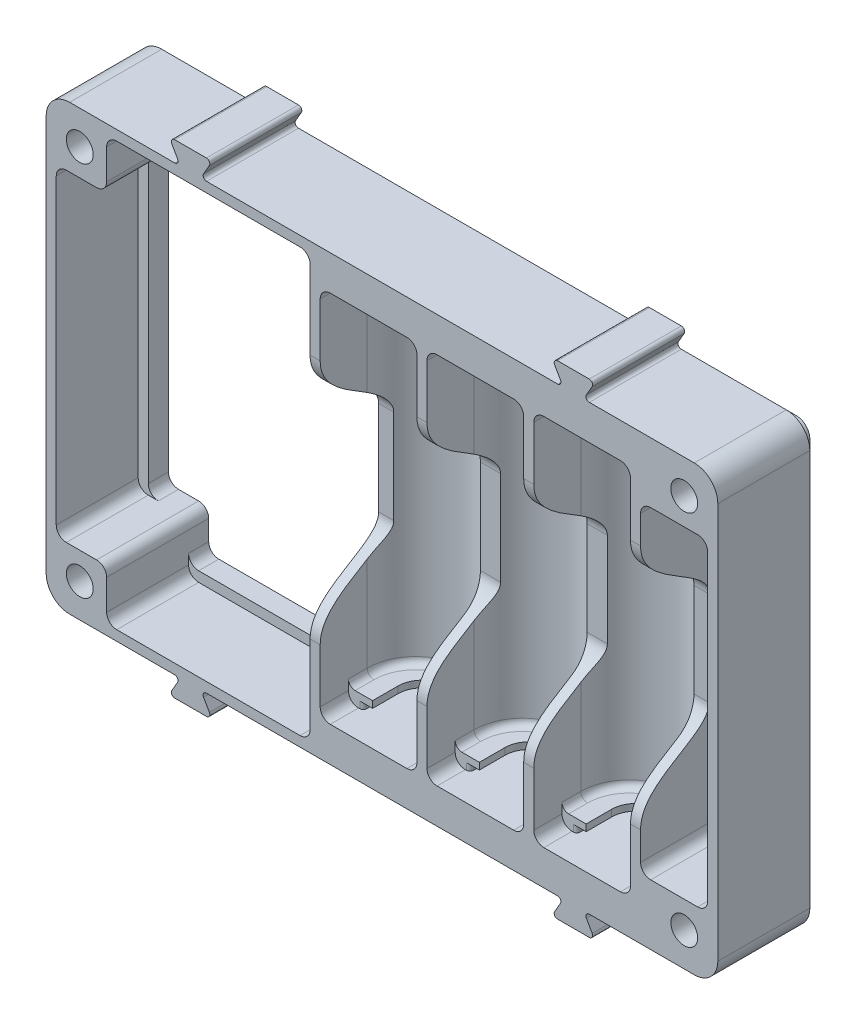
SolidWorks part; units mm, degrees
material "ABS"
ref_plane "Front Plane" through (0, 0, 0) normal (0, 0, 1) x (1, 0, 0)
ref_plane "Top Plane" through (0, 0, 0) normal (0, 1, 0) x (1, 0, 0)
ref_plane "Right Plane" through (0, 0, 0) normal (1, 0, 0) x (0, 0, -1)
sketch "Sketch1" plane through (0, 0, 0) normal (0, 1, 0) x (1, 0, 0)
  line L0 (-24.6, 0) -> (24.6, 0)
  line L1 (0, 0) -> (0, -8.2) construction
  line L2 (-5.4908, -1) -> (5.6475, -1) construction
  line L3 (7, -12.213) -> (7, -2.6204) construction
  line L4 (8.9, -12.0066) -> (8.9, -2.0587) construction
  line L5 (0, -8.2) -> (15.9, -8.2) construction
  line L6 (7.2, -8.2) -> (7.2, -15.2)
  line L7 (8.7, -8.2) -> (8.7, -15.2)
  line L8 (8.7, -15.2) -> (23.1, -15.2) construction
  line L9 (8.7, -15.2) -> (7.2, -15.2)
  line L10 (-1.7094, -15.2) -> (7.2, -15.2) construction
  line L11 (15.9, -8.2) -> (23.1, -8.2) construction
  line L12 (23.1, -15.2) -> (23.1, -8.2)
  line L13 (23.1, -15.2) -> (24.6, -15.2)
  line L14 (24.6, -15.2) -> (24.6, 0)
  line L15 (-24.6, -15.2) -> (-24.6, 0)
  line L16 (-23.1, -15.2) -> (-24.6, -15.2)
  line L17 (-23.1, -15.2) -> (-23.1, -8.2)
  line L18 (-8.7, -8.2) -> (-8.7, -15.2)
  line L19 (-8.7, -15.2) -> (-7.2, -15.2)
  line L20 (-7.2, -8.2) -> (-7.2, -15.2)
  circle A0 centre (0, -8.2) radius 7 construction
  arc A1 (-7.2, -8.2) -> (7.2, -8.2) centre (0, -8.2) cw
  circle A2 centre (15.9, -8.2) radius 7 construction
  arc A3 (8.7, -8.2) -> (23.1, -8.2) centre (15.9, -8.2) cw
  arc A4 (-8.7, -8.2) -> (-23.1, -8.2) centre (-15.9, -8.2) ccw
  dimension "D1" = 14
  dimension "D2" = 0.2
  dimension "D3" = 1
  dimension "D4" = 1.5
  dimension "D5" = 15.2
  dimension "D6" = 15.9
extrude "Boss-Extrude1" add sketch "Sketch1" along normal blind 27.8
sketch "Sketch2" plane through (0, 27.8, 0) normal (0, -1, 0) x (1, 0, 0)
  line L1 (-24.6, 15.2) -> (24.6, 15.2)
  line L2 (-24.6, 15.2) -> (-24.6, 0)
  line L3 (-24.6, 0) -> (24.6, 0)
  line L4 (24.6, 15.2) -> (24.6, 0)
extrude "Boss-Extrude2" add sketch "Sketch2" against normal blind 1.5
ref_plane "Plane1" through (-15.9, 0, 0) normal (1, 0, 0) x (0, 0, -1)
ref_plane "Plane3" through (15.9, 0, 0) normal (1, 0, 0) x (0, 0, -1)
sketch "Sketch6" plane through (0, 0, 0) normal (1, 0, 0) x (0, 0, -1)
  line L0 (-5, 0) -> (-15.2, 0)
  line L1 (-15.2, 0) -> (0, 0) construction
  line L2 (-15.2, 0) -> (-15.2, 18.3)
  line L3 (-15.2, 29.3) -> (-15.2, 0) construction
  line L4 (-5, 0) -> (-5, 7)
  line L5 (0, 29.3) -> (0, 0) construction
  line L6 (0, 29.3) -> (-15.2, 29.3) construction
  spline S0 degree 3 poles (-15.2, 18.3) (-15.2, 12.3) (-5, 11) (-5, 7) knots 0 0 0 0 1 1 1 1
  dimension "D4" = 12
  dimension "D5" = 18
  dimension "D1" = 7
  dimension "D2" = 5
  dimension "D3" = 11
extrude "Cut-Extrude2" cut sketch "Sketch6" against normal through all both and the other way through all
sketch "Sketch3" plane through (0, 27.8, 0) normal (0, -1, 0) x (1, 0, 0)
  line L0 (-10.4, 11) -> (-8.7, 11)
  line L1 (-8.7, 8.2) -> (-8.7, 15.2) construction
  line L2 (-8.7, 11) -> (-8.7, 0)
  line L3 (24.6, 0) -> (-24.6, 0) construction
  line L4 (-8.7, 0) -> (-23.1, 0)
  line L6 (-20.4, 2.9) -> (-11.4, 2.9)
  line L7 (-10.9, 3.4) -> (-10.9, 10.5)
  line L8 (-15.9, 15.2) -> (-15.9, 0) construction
  line L9 (-8.7, 15.2) -> (-23.1, 15.2) construction
  line L19 (-23.1, 11) -> (-23.1, 0)
  line L20 (-21.4, 11) -> (-23.1, 11)
  line L21 (-20.9, 3.4) -> (-20.9, 10.5)
  arc A1 (-11.4, 2.9) -> (-10.9, 3.4) centre (-11.4, 3.4) ccw
  arc A4 (-10.4, 11) -> (-10.9, 10.5) centre (-10.4, 10.5) ccw
  arc A6 (-20.4, 2.9) -> (-20.9, 3.4) centre (-20.4, 3.4) cw
  arc A7 (-21.4, 11) -> (-20.9, 10.5) centre (-21.4, 10.5) cw
  dimension "D6" = 0.5
  dimension "D7" = 0.5
  dimension "D1" = 5
  dimension "D2" = 11
  dimension "D3" = 2.9
extrude "Inner" add sketch "Sketch3" along normal blind 1
sketch "Sketch4" plane through (0, 26.8, 0) normal (0, -1, 0) x (1, 0, 0)
  line L1 (-8.7, 8.2) -> (-8.7, 15.2) construction
  line L2 (-8.7, 11) -> (-8.7, 0)
  line L3 (24.6, 0) -> (-24.6, 0) construction
  line L4 (-8.7, 0) -> (-23.1, 0)
  line L5 (-23.1, 0) -> (-23.1, 11)
  line L6 (-8.7, 11) -> (-10.4, 11) construction
  line L7 (-23.1, 11) -> (-19.5, 11)
  line L8 (-19.5, 11) -> (-19.5, 7.2)
  line L10 (-12.3, 7.2) -> (-12.3, 11)
  line L11 (-12.3, 11) -> (-8.7, 11)
  arc A0 (-19.5, 7.2) -> (-12.3, 7.2) centre (-15.9, 7.2) ccw
  dimension "D1" = 3.6
  dimension "D2" = 3.8
extrude "Boss-Extrude4" add sketch "Sketch4" along normal blind 1
sketch "Sketch5" plane through (0, 0, 15.2) normal (0, 0, 1) x (1, 0, 0)
  line L0 (-8.7, 27.8) -> (-23.1, 27.8) construction
  line L1 (-17.6, 27.8) -> (-14.2, 27.8)
  line L2 (-17.6, 27.8) -> (-17.6, 27.3)
  line L3 (-17.6, 27.3) -> (-14.2, 27.3)
  line L4 (-14.2, 27.8) -> (-14.2, 27.3)
  point P10 (-15.9, 27.8)
  dimension "D1" = 0.5
  dimension "D2" = 3.4
extrude "Cut-Extrude1" cut sketch "Sketch5" against normal through all
sketch "Sketch10" plane through (0, 0, 0) normal (0, 0, 1) x (1, 0, 0)
  line L0 (-24.6, 29.3) -> (24.6, 29.3) construction
  line L1 (-14.2, 27.3) -> (-17.6, 27.3)
  line L2 (-14.2, 27.3) -> (-14.2, 29.3)
  line L3 (-14.2, 29.3) -> (-17.6, 29.3)
  line L4 (-17.6, 27.3) -> (-17.6, 29.3)
extrude "Cut-Extrude6" cut sketch "Sketch10" along normal blind 0.6
mirror "Mirror1" about plane through (0, 0, 0) normal (1, 0, 0) of "Cut-Extrude6", "Inner", "Boss-Extrude4", "Cut-Extrude1"
ref_plane "Plane2" through (-7.95, 0, 0) normal (1, 0, 0) x (0, 0, -1)
mirror "Mirror2" about plane through (-7.95, 0, 0) normal (1, 0, 0) of "Cut-Extrude6", "Inner", "Boss-Extrude4", "Cut-Extrude1"
fillet "Fillet2" radius 1.5 6 edges at (-8.7, 27.8, 13.1) (-23.1, 27.8, 13.1) (8.7, 27.8, 13.1) (23.1, 27.8, 13.1) (7.2, 27.8, 13.1) (-7.2, 27.8, 13.1)
fillet "Fillet3" radius 1 9 edges at (-8.7, 25.8, 9.6) (-15.9, 25.8, 1) (-23.1, 25.8, 9.6) (23.1, 25.8, 9.6) (8.7, 25.8, 9.6) (7.2, 25.8, 9.6) (-7.2, 25.8, 9.6) (15.9, 25.8, 1) (0, 25.8, 1)
mirror "Mirror4" about plane through (0, 0, 0) normal (0, 1, 0) of bodies 108 110
sketch "Эскиз1" plane through (0, 0, 0) normal (0, 0, -1) x (-1, 0, 0)
  line L0 (-24.6, 29.3) -> (-24.6, -29.3) construction
  line L5 (-36.1, 33) -> (63.9, 33)
  line L6 (-36.1, 33) -> (-36.1, -33)
  line L7 (-36.1, -33) -> (63.9, -33)
  line L8 (63.9, 33) -> (63.9, -33)
  line L9 (-36.1, 33) -> (63.9, -33) construction
  line L10 (-36.1, -33) -> (63.9, 33) construction
  line L11 (-34.6, -31.5) -> (62.4, -31.5)
  line L12 (-34.6, -31.5) -> (-34.6, 31.5)
  line L13 (-34.6, 31.5) -> (62.4, 31.5)
  line L14 (62.4, -31.5) -> (62.4, 31.5)
  line L15 (-34.6, -31.5) -> (62.4, 31.5) construction
  line L16 (-34.6, 31.5) -> (62.4, -31.5) construction
  line L17 (24.6, 29.3) -> (24.6, -29.3) construction
  line L18 (-24.6, 29.3) -> (24.6, 29.3)
  line L19 (-24.6, 29.3) -> (-24.6, 31.5)
  line L20 (-24.6, 31.5) -> (24.6, 31.5)
  line L21 (24.6, 29.3) -> (24.6, 31.5)
  line L22 (-24.6, -29.3) -> (24.6, -29.3)
  line L23 (-24.6, -29.3) -> (-24.6, -31.5)
  line L24 (-24.6, -31.5) -> (24.6, -31.5)
  line L25 (24.6, -29.3) -> (24.6, -31.5)
  line L27 (-24.6, 29.3) -> (-24.6, -29.3) construction
  line L28 (62.4, 31.5) -> (54.9, 31.5)
  line L29 (62.4, 31.5) -> (62.4, 24)
  line L30 (62.4, 24) -> (54.9, 24)
  line L31 (54.9, 31.5) -> (54.9, 24)
  line L32 (62.4, -31.5) -> (54.9, -31.5)
  line L33 (62.4, -31.5) -> (62.4, -24)
  line L34 (62.4, -24) -> (54.9, -24)
  line L35 (54.9, -31.5) -> (54.9, -24)
  line L36 (-34.6, 31.5) -> (-24.6, 31.5)
  line L37 (-34.6, 31.5) -> (-34.6, 24)
  line L38 (-34.6, 24) -> (-24.6, 24)
  line L39 (-24.6, 31.5) -> (-24.6, 24)
  line L41 (-34.6, -31.5) -> (-24.6, -31.5)
  line L42 (-34.6, -31.5) -> (-34.6, -24)
  line L43 (-34.6, -24) -> (-24.6, -24)
  line L44 (-24.6, -31.5) -> (-24.6, -24)
  point P0 (13.9, 0)
  point P5 (13.9, 0)
  point P13 (0, 0)
  line M16 (24.6, 29.3) -> (17.6, 29.3)
  line M20 (14.2, 29.3) -> (1.7, 29.3)
  line M24 (-1.7, 29.3) -> (-14.2, 29.3)
  line M28 (-17.6, 29.3) -> (-24.6, 29.3)
  line M30 (-24.6, 29.3) -> (-24.6, -29.3)
  dimension "D1" = 100
  dimension "D2" = 66
  dimension "D3" = 1.5
  dimension "D4" = 1.5
  dimension "D5" = 10
  dimension "D6" = 7.5
extrude "Бобышка-Вытянуть1" add sketch "Эскиз1" against normal up to surface (15.2 mm away) contours L13 L31 L30 L14 | L35 L11 L14 L34 | L43 L12 L11 L23 M30 | L12 L38 L19 L13 M30 | L8 L5 L6 L7 L14 L11 L12 L13 | L21 L13 L19 L18 M16 M28 M24 M20 | L23 L22 L25 L24 region at (-13.9, 31.8018, 0) region at (29.6, -27.75, 0) region at (29.6, 27.75, 0) region at (-58.65, -27.75, 0) region at (0, 30.4, 0) region at (-58.65, 27.75, 0) up to face at (0, -24.1575, 15.2)
sketch "Эскиз2" plane through (0, 0, 0) normal (0, 0, -1) x (-1, 0, 0)
  line L0 (62.4, -24) -> (62.4, 24) construction
  line L1 (-34.6, -31.5) -> (62.4, -31.5)
  line L2 (-34.6, -31.5) -> (-34.6, 31.5)
  line L3 (-34.6, 31.5) -> (62.4, 31.5)
  line L4 (62.4, -31.5) -> (62.4, 31.5)
  line L5 (-34.6, -24) -> (-34.6, 24) construction
  line L6 (24.6, 31.5) -> (54.9, 31.5) construction
  line L7 (24.6, -31.5) -> (54.9, -31.5) construction
  line L8 (-24.6, 24) -> (-24.6, -24) construction
  line L11 (-34.6, 24) -> (-24.6, 24)
  line L12 (-24.6, 31.5) -> (-24.6, 24)
  line L13 (54.9, 24) -> (62.4, 24)
  line L14 (54.9, 24) -> (54.9, 31.5)
  line L17 (54.9, -24) -> (62.4, -24)
  line L18 (54.9, -24) -> (54.9, -31.5)
  line L23 (-34.6, -24) -> (-24.6, -24)
  line L24 (-24.6, -31.5) -> (-24.6, -24)
  line L25 (-24.6, 30) -> (54.9, 30)
  line L26 (-24.6, -30) -> (54.9, -30)
  line L27 (-33.1, 24) -> (-33.1, -24)
  line L28 (60.9, -24) -> (60.9, 24)
  line L29 (62.4, 24) -> (54.9, 24) construction
  line M25 (-34.6, 24) -> (-24.6, 24)
  line M27 (-24.6, -24) -> (-34.6, -24)
  line M28 (-34.6, -24) -> (-34.6, 24)
  line M29 (24.6, -31.5) -> (24.6, 31.5)
  line M30 (24.6, 31.5) -> (54.9, 31.5)
  line M31 (54.9, 31.5) -> (54.9, 24)
  line M32 (54.9, 24) -> (62.4, 24)
  line M33 (62.4, 24) -> (62.4, -24)
  line M34 (62.4, -24) -> (54.9, -24)
  line M35 (54.9, -24) -> (54.9, -31.5)
  line M36 (54.9, -31.5) -> (24.6, -31.5)
  dimension "D1" = 1.5
  dimension "D2" = 1.5
  dimension "D3" = 1.5
  dimension "D4" = 1.5
extrude "Бобышка-Вытянуть2" add sketch "Эскиз2" against normal blind 3 contours L12 L3 L2 L11 M25 | L12 L25 L3 M29 | L25 M29 M31 M30 | L13 L4 L3 L14 M32 M31 | L28 L13 M34 M33 | L1 L4 L17 L18 M34 M35 | L26 L18 M29 M36 | L26 L24 L1 M29 | L1 L24 L23 L2 M27 | L27 L23 M25 M28 region at (29.6, -27.75, 0) region at (0, -30.75, 0) region at (33.85, 0, 0) region at (-39.75, -30.75, 0) region at (29.6, 27.75, 0) region at (-58.65, -27.75, 0) region at (-39.75, 30.75, 0) region at (0, 30.75, 0) region at (-61.65, 0, 0) region at (-58.65, 27.75, 0)
fillet "Скругление6" radius 3.5 4 edges at (36.1, 33, 7.6) (36.1, -33, 7.6) (-63.9, -33, 7.6) (-63.9, 33, 7.6)
sketch "Эскиз8" plane through (0, 0, 0) normal (0, 0, -1) x (-1, 0, 0)
  line L8 (62.4, -29.5) -> (62.4, 29.5)
  line L9 (-32.6, -31.5) -> (60.4, -31.5)
  line L10 (-34.6, 29.5) -> (-34.6, -29.5)
  line L11 (60.4, 31.5) -> (-32.6, 31.5)
  line L12 (62.4, -29.5) -> (62.4, 29.5)
  line L13 (-32.6, -31.5) -> (60.4, -31.5)
  line L14 (-34.6, 29.5) -> (-34.6, -29.5)
  line L15 (60.4, 31.5) -> (-32.6, 31.5)
  line L20 (63.9, -29.5) -> (63.9, 29.5)
  line L21 (-32.6, -33) -> (60.4, -33)
  line L22 (-36.1, 29.5) -> (-36.1, -29.5)
  line L23 (60.4, 33) -> (-32.6, 33)
  line L24 (63.9, -29.5) -> (63.9, 29.5)
  line L25 (-32.6, -33) -> (60.4, -33)
  line L26 (-36.1, 29.5) -> (-36.1, -29.5)
  line L27 (60.4, 33) -> (-32.6, 33)
  arc A8 (62.4, 29.5) -> (60.4, 31.5) centre (60.4, 29.5) ccw
  arc A9 (60.4, -31.5) -> (62.4, -29.5) centre (60.4, -29.5) ccw
  arc A10 (-34.6, -29.5) -> (-32.6, -31.5) centre (-32.6, -29.5) ccw
  arc A11 (-32.6, 31.5) -> (-34.6, 29.5) centre (-32.6, 29.5) ccw
  arc A12 (62.4, 29.5) -> (60.4, 31.5) centre (60.4, 29.5) ccw
  arc A13 (60.4, -31.5) -> (62.4, -29.5) centre (60.4, -29.5) ccw
  arc A14 (-34.6, -29.5) -> (-32.6, -31.5) centre (-32.6, -29.5) ccw
  arc A15 (-32.6, 31.5) -> (-34.6, 29.5) centre (-32.6, 29.5) ccw
  arc A20 (63.9, 29.5) -> (60.4, 33) centre (60.4, 29.5) ccw
  arc A21 (60.4, -33) -> (63.9, -29.5) centre (60.4, -29.5) ccw
  arc A22 (-36.1, -29.5) -> (-32.6, -33) centre (-32.6, -29.5) ccw
  arc A23 (-32.6, 33) -> (-36.1, 29.5) centre (-32.6, 29.5) ccw
  arc A24 (63.9, 29.5) -> (60.4, 33) centre (60.4, 29.5) ccw
  arc A25 (60.4, -33) -> (63.9, -29.5) centre (60.4, -29.5) ccw
  arc A26 (-36.1, -29.5) -> (-32.6, -33) centre (-32.6, -29.5) ccw
  arc A27 (-32.6, 33) -> (-36.1, 29.5) centre (-32.6, 29.5) ccw
  dimension "D1" = 1.5
  dimension "D2" = 0
extrude "Вырез-Вытянуть1" cut sketch "Эскиз8" against normal blind 1.5
fillet "Скругление7" radius 1.5 20 edges at (-24.6, -31.5, 9.1) (-24.6, -30, 1.5) (-54.9, -30, 1.5) (-54.9, -31.5, 9.1) (-54.9, -24, 7.6) (-24.6, 30, 1.5) (-24.6, 31.5, 9.1) (-54.9, 30, 1.5) (-54.9, 31.5, 9.1) (-54.9, 24, 7.6) (-60.9, 24, 1.5) (-62.4, 24, 9.1) (-60.9, -24, 1.5) (-62.4, -24, 9.1) (34.6, 24, 9.1) (34.6, -24, 9.1) (33.1, -24, 1.5) (24.6, -24, 7.6) (24.6, 24, 7.6) (33.1, 24, 1.5)
sketch "Эскиз11" plane through (0, 0, 15.2) normal (0, 0, 1) x (1, 0, 0)
  line L0 (-43.9, 33) -> (-45.6321, 36)
  line L2 (-45.6321, 36) -> (-39.1679, 36)
  line L3 (-39.1679, 36) -> (-40.9, 33)
  line L4 (-40.9, 33) -> (-43.9, 33)
  line L5 (13.1, 33) -> (11.3679, 36)
  line L6 (11.3679, 36) -> (17.8321, 36)
  line L7 (17.8321, 36) -> (16.1, 33)
  line L8 (16.1, 33) -> (13.1, 33)
  line L11 (-43.9, -33) -> (-45.6321, -36)
  line L13 (-45.6321, -36) -> (-39.1679, -36)
  line L14 (-39.1679, -36) -> (-40.9, -33)
  line L15 (-40.9, -33) -> (-43.9, -33)
  line L16 (13.1, -33) -> (11.3679, -36)
  line L17 (11.3679, -36) -> (17.8321, -36)
  line L18 (17.8321, -36) -> (16.1, -33)
  line L19 (16.1, -33) -> (13.1, -33)
  line L20 (-60.4, -33) -> (32.6, -33) construction
  line L21 (-60.4, 33) -> (32.6, 33) construction
  line L22 (-63.9, -29.5) -> (-63.9, 29.5) construction
  line L23 (36.1, -29.5) -> (36.1, 29.5) construction
  point P2 (10.48, 33)
  point P18 (-43.52, -33)
  point P22 (10.48, -33)
  point P25 (13.48, -33)
  point P29 (-46.52, 33)
  dimension "D1" = 60
  dimension "D2" = 3
  dimension "D3" = 3
  dimension "D4" = 3
  dimension "D5" = 20
  dimension "D6" = 20
  dimension "D7" = 3
extrude "Бобышка-Вытянуть3" add sketch "Эскиз11" against normal up to surface (13.7 mm away) up to face at (-13.9, 0, 1.5)
fillet "Скругление8" radius 0.5 16 edges at (-45.6321, -36, 8.35) (-43.9, -33, 8.35) (-39.1679, -36, 8.35) (-40.9, -33, 8.35) (17.8321, -36, 8.35) (16.1, -33, 8.35) (11.3679, -36, 8.35) (13.1, -33, 8.35) (16.1, 33, 8.35) (17.8321, 36, 8.35) (13.1, 33, 8.35) (11.3679, 36, 8.35) (-43.9, 33, 8.35) (-40.9, 33, 8.35) (-39.1679, 36, 8.35) (-45.6321, 36, 8.35)
sketch "Эскиз3" plane through (0, 0, 15.2) normal (0, 0, 1) x (1, 0, 0)
  line L4 (-60.4, 33) -> (-44.766, 33) construction
  line L5 (-63.9, -29.5) -> (-63.9, 29.5) construction
  line L6 (36.1, -29.5) -> (36.1, 29.5) construction
  line L7 (-60.4, -33) -> (-44.766, -33) construction
  circle A0 centre (-58.9, 28) radius 2
  circle A1 centre (31.1, 28) radius 2
  circle A2 centre (31.1, -28) radius 2
  circle A3 centre (-58.9, -28) radius 2
  point P0 (-58.9, 28)
  point P1 (31.1, 28)
  point P2 (31.1, -28)
  point P3 (-58.9, -28)
  dimension "D5" = 4
  dimension "D1" = 5
  dimension "D2" = 5
  dimension "D3" = 5
  dimension "D4" = 5
sketch "Эскиз12" plane through (0, 0, 0) normal (0, 0, -1) x (-1, 0, 0)
  circle A0 centre (-31.1, 28) radius 2
  circle A1 centre (58.9, 28) radius 2
  circle A2 centre (58.9, -28) radius 2
  circle A3 centre (-31.1, -28) radius 2
  point P8 (58.9, 28)
  point P9 (58.9, -28)
  point P10 (-31.1, -28)
  point P11 (0, 0)
  point P12 (-31.1, 28)
  point P13 (62.02, 28.5)
  point P18 (62.02, -28.5)
  point P19 (-28.98, -28.5)
  point P20 (-28.98, 28.5)
  dimension "D1" = 4
extrude "Вырез-Вытянуть2" cut sketch "Эскиз12" against normal blind 4.2
extrude "Вырез-Вытянуть3" cut sketch "Эскиз3" against normal blind 4.2
